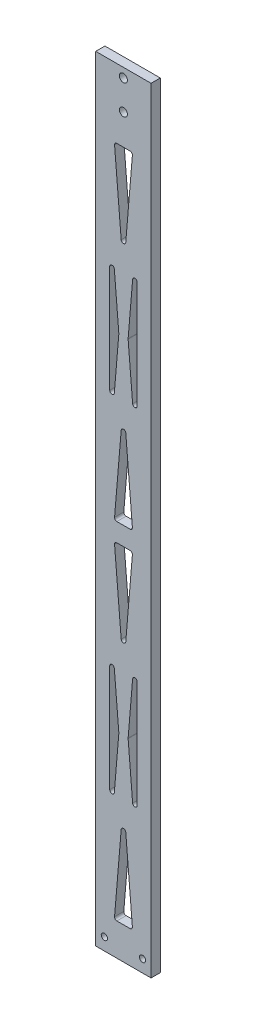
SolidWorks part; units mm, degrees
ref_plane "Front Plane" through (0, 0, 0) normal (0, 0, 1) x (1, 0, 0)
ref_plane "Top Plane" through (0, 0, 0) normal (0, 1, 0) x (1, 0, 0)
ref_plane "Right Plane" through (0, 0, 0) normal (1, 0, 0) x (0, 0, -1)
sketch "Sketch1" plane through (0, 0, 0) normal (0, 0, 1) x (1, 0, 0)
  line L1 (-25.4, -292.1) -> (-25.4, 241.3) construction
  line L2 (-25.4, 241.3) -> (12.7, 241.3)
  line L3 (-25.4, 241.3) -> (-25.4, -292.1)
  line L4 (-25.4, -292.1) -> (12.7, -292.1)
  line L5 (12.7, 241.3) -> (12.7, -292.1)
  point P6 (-25.4, -25.4)
  dimension "D1" = 533.4
  dimension "D2" = 38.1
  dimension "D3" = 12.7
  dimension "D4" = 241.3
extrude "Boss-Extrude1" add sketch "Sketch1" along normal mid plane 6.35
sketch "Sketch2" plane through (0, 0, 3.175) normal (0, 0, 1) x (1, 0, 0)
  line L0 (12.7, 241.3) -> (-25.4, 241.3) construction
  line L1 (-6.35, 241.3) -> (-6.35, 205.7623) construction
  circle A0 centre (-6.35, 234.95) radius 2.7781
  circle A1 centre (-6.35, 214.63) radius 2.7781
  dimension "D3" = 5.5562
  dimension "D1" = 6.35
  dimension "D2" = 20.32
extrude "Cut-Extrude1" cut sketch "Sketch2" against normal through all
sketch "Sketch3" plane through (0, 0, 3.175) normal (0, 0, 1) x (1, 0, 0)
  line L0 (12.7, -292.1) -> (12.7, 241.3) construction
  line L1 (12.7, 203.2) -> (-25.2838, 203.2)
  line L2 (12.7, 203.2) -> (12.7, -279.3892)
  line L3 (12.7, -279.3892) -> (-25.2838, -279.3892)
  line L4 (-25.2838, 203.2) -> (-25.2838, -279.3892)
  line L5 (12.7, 241.3) -> (-25.4, 241.3) construction
  line L6 (-25.4, -292.1) -> (12.7, -292.1) construction
  line L7 (3.175, 193.675) -> (-15.7588, 193.675)
  line L8 (-15.7588, 193.675) -> (-15.7588, -269.8642)
  line L9 (3.175, -269.8642) -> (-15.7588, -269.8642)
  line L10 (3.175, 193.675) -> (3.175, -269.8642)
  line L11 (3.175, -38.0946) -> (-15.7588, -38.0946) construction
  line L14 (3.175, -31.7446) -> (-15.7588, -31.7446)
  line L17 (3.175, -44.4446) -> (-15.7588, -44.4446)
  line L20 (3.175, 193.675) -> (-15.7588, -31.7446) construction
  line L23 (6.3389, 193.4093) -> (-12.5949, -32.0104)
  line L26 (0.0111, 193.9407) -> (-18.9226, -31.4789)
  line L27 (-15.7588, 193.675) -> (3.175, -31.7446) construction
  line L28 (-12.5949, 193.9407) -> (6.3389, -31.4789)
  line L29 (-18.9226, 193.4093) -> (0.0111, -32.0104)
  line L30 (3.175, -269.8642) -> (-15.7588, -44.4446) construction
  line L31 (6.3389, -269.5985) -> (-12.5949, -44.1789)
  line L32 (0.0111, -270.13) -> (-18.9226, -44.7104)
  line L33 (-15.7588, -269.8642) -> (3.175, -44.4446) construction
  line L34 (-12.5949, -270.13) -> (6.3389, -44.7104)
  line L35 (-18.9226, -269.5985) -> (0.0111, -44.1789)
  arc A10 (6.3389, 193.4093) -> (0.0111, 193.9407) centre (3.175, 193.675) ccw
  arc A11 (-18.9226, -31.4789) -> (-12.5949, -32.0104) centre (-15.7588, -31.7446) ccw
  arc A12 (-12.5949, 193.9407) -> (-18.9226, 193.4093) centre (-15.7588, 193.675) ccw
  arc A13 (0.0111, -32.0104) -> (6.3389, -31.4789) centre (3.175, -31.7446) ccw
  arc A14 (6.3389, -269.5985) -> (0.0111, -270.13) centre (3.175, -269.8642) cw
  arc A15 (-18.9226, -44.7104) -> (-12.5949, -44.1789) centre (-15.7588, -44.4446) cw
  arc A16 (-12.5949, -270.13) -> (-18.9226, -269.5985) centre (-15.7588, -269.8642) cw
  arc A17 (0.0111, -44.1789) -> (6.3389, -44.7104) centre (3.175, -44.4446) cw
  point P20 (-6.2919, 80.9652)
  point P25 (-6.2919, 80.9652)
  point P30 (-6.2919, -157.1544)
  point P35 (-6.2919, -157.1544)
  dimension "D5" = 12.7
  dimension "D6" = 3.175
  dimension "D1" = 37.9838
  dimension "D2" = 38.1
  dimension "D3" = 12.7108
  dimension "D4" = 9.525
extrude "Cut-Extrude2" cut sketch "Sketch3" against normal through all contours L7 L28 L26 | L23 L28 L10 | L29 L8 L26 | L29 L23 L14 | L31 L35 L17 | L34 L31 L10 | L8 L35 L32 | L34 L9 L32 region at (-6.2919, 168.7496, 3.175) region at (1.0814, 80.9652, 3.175) region at (-13.6652, 80.9652, 3.175) region at (-6.2919, -6.8193, 3.175) region at (1.0814, -157.1544, 3.175) region at (-6.2919, -69.37, 3.175) region at (-13.6652, -157.1544, 3.175) region at (-6.2919, -244.9389, 3.175)
fillet "Fillet1" radius 1.5875 24 edges at (3.175, -82.3783, 0) (-12.5726, -44.4446, 0) (-0.0112, -44.4446, 0) (-6.2919, -119.2207, 0) (-9.4781, 80.9652, 0) (-15.7588, 6.1891, 0) (-15.7588, 155.7413, 0) (3.175, 6.1891, 0) (-3.1057, 80.9652, 0) (3.175, 155.7413, 0) (3.175, -231.9305, 0) (-3.1057, -157.1544, 0) (-12.5726, 193.675, 0) (-0.0112, 193.675, 0) (-9.4781, -157.1544, 0) (-15.7588, -231.9305, 0) (-15.7588, -82.3783, 0) (-6.2919, -195.0881, 0) (-0.0112, -269.8642, 0) (-12.5726, -269.8642, 0) (-0.0112, -31.7446, 0) (-12.5726, -31.7446, 0) (-6.2919, 43.0315, 0) (-6.2919, 118.8989, 0)
sketch "Sketch4" plane through (0, 0, 3.175) normal (0, 0, 1) x (1, 0, 0)
  line L0 (-6.2919, -269.8642) -> (-6.2919, -287.5063)
  line L1 (-1.7376, -269.8642) -> (-10.8461, -269.8642) construction
  circle A0 centre (6.858, -283.591) radius 2.1526
  circle A1 centre (6.858, -283.591) radius 2.54 construction
  circle A2 centre (-19.4418, -283.591) radius 2.1526
  dimension "D1" = 4.3053
extrude "Cut-Extrude3" cut sketch "Sketch4" against normal through all contours A0 | A2 region at (6.858, -283.591, 3.175) region at (-19.4418, -283.591, 3.175)
move or copy body "Body-Move/Copy1" [suppressed] bodies to move or copy 102 parameters "D1"=0, "D2"=0, "D3"=0
